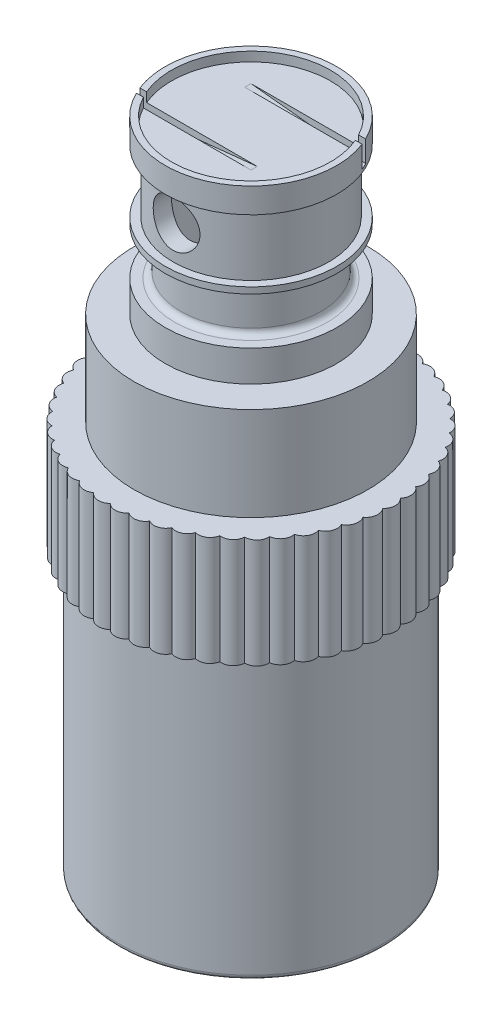
SolidWorks part; units mm, degrees
material "Brass"
ref_plane "Front Plane" through (0, 0, 0) normal (0, 0, 1) x (1, 0, 0)
ref_plane "Top Plane" through (0, 0, 0) normal (0, 1, 0) x (1, 0, 0)
ref_plane "Right Plane" through (0, 0, 0) normal (1, 0, 0) x (0, 0, -1)
sketch "Sketch1" plane through (0, 0, 0) normal (0, 1, 0) x (1, 0, 0)
  circle A0 centre (0, 0) radius 4.25
  dimension "D1" = 8.5
extrude "Boss-Extrude1" add sketch "Sketch1" along normal blind 12.5
sketch "Sketch4" plane through (0, 12.5, 0) normal (0, 1, 0) x (1, 0, 0)
  circle A0 centre (0, 0) radius 4.25 construction
  arc A1 (-4.233, 0.3796) -> (-4.233, -0.3796) centre (0, 0) ccw
  arc A2 (-4.233, 0.3796) -> (-4.233, -0.3796) centre (-4.25, 0) ccw
  dimension "D1" = 0.76
extrude "Boss-Extrude4" add sketch "Sketch4" against normal blind 3.5
pattern_circular "CirPattern5" count 50 over 360 about axis through (0, 12.5, 0) along (0, -1, 0) of "Boss-Extrude4" reverse direction yes
sketch "Sketch5" plane through (0, 12.5, 0) normal (0, 1, 0) x (1, 0, 0)
  circle A0 centre (0, 0) radius 3.75
  dimension "D1" = 7.5
extrude "Boss-Extrude5" add sketch "Sketch5" along normal blind 3
sketch "Sketch6" plane through (0, 15.5, 0) normal (0, 1, 0) x (1, 0, 0)
  circle A0 centre (0, 0) radius 2.75
  dimension "D1" = 5.5
extrude "Boss-Extrude6" add sketch "Sketch6" along normal blind 1
sketch "Sketch7" plane through (0, 16.5, 0) normal (0, 1, 0) x (1, 0, 0)
  circle A0 centre (0, 0) radius 2.25
  dimension "D1" = 4.5
extrude "Boss-Extrude7" add sketch "Sketch7" along normal blind 1.5
sketch "Sketch8" plane through (0, 18, 0) normal (0, 1, 0) x (1, 0, 0)
  circle A0 centre (0, 0) radius 2.75
  dimension "D1" = 5.5
extrude "Boss-Extrude8" add sketch "Sketch8" along normal blind 0.2
sketch "Sketch9" plane through (0, 18.2, 0) normal (0, 1, 0) x (1, 0, 0)
  circle A0 centre (0, 0) radius 2.5
  dimension "D1" = 5
extrude "Boss-Extrude9" add sketch "Sketch9" along normal blind 2
sketch "Sketch10" plane through (0, 20.2, 0) normal (0, 1, 0) x (1, 0, 0)
  circle A0 centre (0, 0) radius 2.75
  dimension "D1" = 5.5
extrude "Boss-Extrude10" add sketch "Sketch10" along normal blind 0.8
sketch "Sketch11" plane through (0, 21, 0) normal (0, 1, 0) x (1, 0, 0)
  circle A0 centre (0, 0) radius 2.55
  circle A1 centre (0, 0) radius 2.75 construction
  dimension "D1" = 0.2
extrude "Cut-Extrude1" cut sketch "Sketch11" against normal blind 0.3
sketch "Sketch12" plane through (0, 20.7, 0) normal (0, 1, 0) x (1, 0, 0)
  line L1 (1.2, 2.4744) -> (1.2, -2.25) construction
  line L2 (-2.9252, -1) -> (1.2, -1)
  line L3 (1.2, -1) -> (1.2, -1.2)
  line L4 (1.2, -1.2) -> (-2.9252, -1.2)
  line L5 (-2.9252, -1.2) -> (-2.9252, -1)
  circle A0 centre (0, 0) radius 2.75 construction
  circle A1 centre (0, 0) radius 2.55 construction
  dimension "D1" = 1.2
  dimension "D2" = 0.2
  dimension "D3" = 1
revolve "Cut-Revolve1" cut sketch "Sketch12" angle 6 about L1 other way angle 6 reverse direction yes
sketch "Sketch13" plane through (0, 20.7, 0) normal (0, 1, 0) x (1, 0, 0)
  line L0 (-1.2, 2.9501) -> (-1.2, -0.6463) construction
  line L1 (-1.2, 1.2) -> (2.8842, 1.2)
  line L2 (2.8842, 1.2) -> (2.8842, 1)
  line L3 (2.8842, 1) -> (-1.2, 1)
  line L4 (-1.2, 1) -> (-1.2, 1.2)
  dimension "D1" = 0.2
  dimension "D2" = 1
  dimension "D3" = 3.5964
  dimension "D4" = 1.2
revolve "Cut-Revolve2" cut sketch "Sketch13" angle 6 about L0 other way angle 6
sketch "Sketch15" plane through (0, 0, 0) normal (0, 0, 1) x (1, 0, 0)
  circle A0 centre (0, 19.271) radius 0.75
  dimension "D1" = 1.5
extrude "Cut-Extrude2" cut sketch "Sketch15" against normal through all both and the other way through all
sketch "Sketch16" plane through (0, 0, 0) normal (0, -1, 0) x (1, 0, 0)
  circle A0 centre (0, 0) radius 3.95
  circle A1 centre (0, 0) radius 4.25 construction
  dimension "D1" = 0.3
extrude "Cut-Extrude3" cut sketch "Sketch16" against normal blind 12.2
sketch "Sketch17" plane through (0, 12.2, 0) normal (0, -1, 0) x (1, 0, 0)
  circle A0 centre (0, 0) radius 3.45
  dimension "D1" = 6.9
extrude "Cut-Extrude4" cut sketch "Sketch17" against normal blind 3
sketch "Sketch19" plane through (0, 15.2, 0) normal (0, -1, 0) x (1, 0, 0)
  circle A0 centre (0, 0) radius 1.95
  dimension "D1" = 3.9
extrude "Cut-Extrude5" cut sketch "Sketch19" against normal up to surface (5 mm away) up to face at (0, 20.2, 2.5)
fillet "Fillet1" radius 0.2 2 edges at (0, 16.5, 2.25) (0, 18, 2.25)
fillet "Fillet2" 2 edges at (0, 0, 4.25) (0, 0, -3.95) type full round first side face at (0, 0, 4.25) second side face at (0, 12.2, -3.95) middle face at (0, 0, -3.95)
